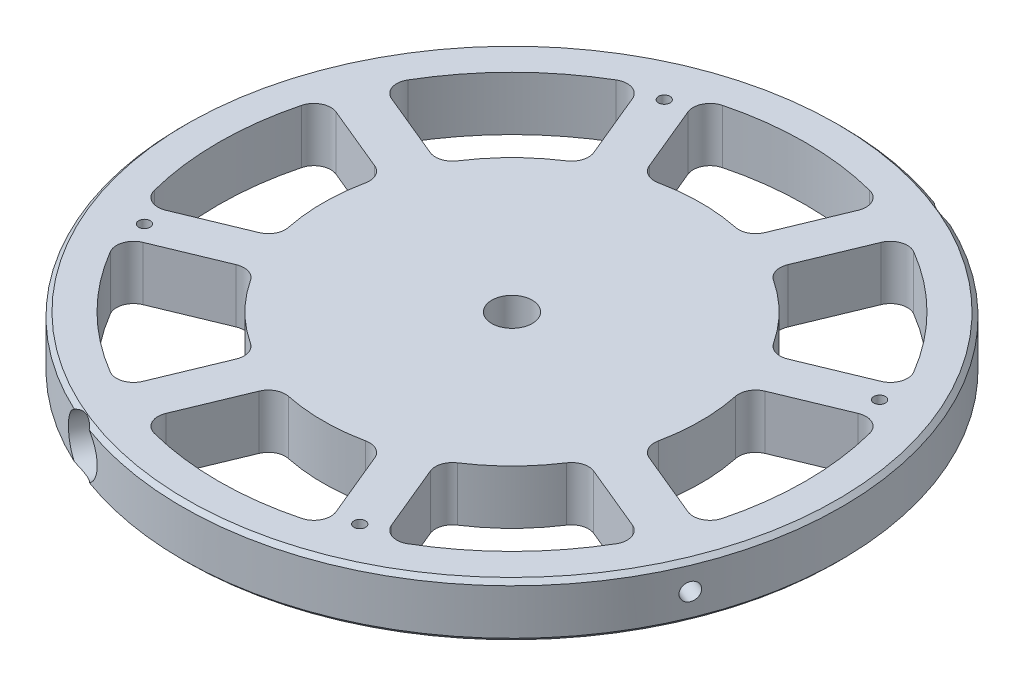
SolidWorks part; units mm, degrees
material "6061-T6 (SS)"
ref_plane "Front Plane" through (0, 0, 0) normal (0, 0, 1) x (1, 0, 0)
ref_plane "Top Plane" through (0, 0, 0) normal (0, 1, 0) x (1, 0, 0)
ref_plane "Right Plane" through (0, 0, 0) normal (1, 0, 0) x (0, 0, -1)
sketch "Sketch2" plane through (0, 0, 0) normal (1, 0, 0) x (0, 0, -1)
  line L0 (0, 0) -> (-77.55, 0)
  line L1 (-77.55, 0) -> (-77.55, 12.7)
  line L2 (-77.55, 12.7) -> (0, 12.7)
  line L5 (0, 12.7) -> (0, 0)
  dimension "D1" = 77.55
  dimension "D2" = 12.7
ref_axis "Axis1" through (0, -0.8888, 0) along (0, 1, 0)
revolve "Revolve1" add sketch "Sketch2" angle 360 about axis through (0, -0.8888, 0) along (0, 1, 0)
hole_wizard "#6-32 Tapped Hole2" positions "Sketch6" profile "Sketch7" tap size "#6-32" standard "ANSI Inch" end condition through all
sketch "Sketch6" plane through (0, 12.7, 0) normal (0, 1, 0) x (1, 0, 0)
  line L0 (0, 0) -> (-53.438, 129.0108) construction
  line L2 (0, 0) -> (0, 109.0908) construction
  point P0 (-25.3336, 61.1608)
  dimension "D1" = 22.5
  dimension "D2" = 66.2
sketch "Sketch7" plane through (-25.3336, 12.7, -61.1608) normal (1, 0, 0) x (0, 0, 1)
  line L0 (0, 0) -> (0, 12.7)
  line L1 (0, 12.7) -> (1.3525, 12.7)
  line L2 (1.3525, 12.7) -> (1.3525, 0)
  line L5 (1.3525, 0) -> (0, 0)
  line L11 (0, -6.35) -> (0, 107.95) construction
  dimension "Thread Major Dia." = 2.7051
  dimension "Thru Tap Drill Depth" = 12.7
pattern_circular "CirPattern3" count 4 over 360 about axis through (0, -0.8888, 0) along (0, 1, 0) of "#6-32 Tapped Hole2"
sketch "Sketch8" plane through (0, 12.7, 0) normal (0, 1, 0) x (1, 0, 0)
  line L4 (0, 0) -> (0, 93.9995) construction
  line L5 (0, 0) -> (113.8372, 0) construction
  line L6 (-12.2829, 42.7192) -> (-21.7355, 65.5398)
  line L7 (12.2829, 42.7192) -> (21.7355, 65.5398)
  line L8 (0, 0) -> (-25.3336, 61.1608) construction
  arc A0 (-12.2829, 42.7192) -> (12.2829, 42.7192) centre (0, 0) cw
  arc A1 (-21.7355, 65.5398) -> (21.7355, 65.5398) centre (0, 0) cw
  circle A2 centre (0, 0) radius 77.55 construction
  dimension "D1" = 44.45
  dimension "D2" = 8.5
  dimension "D3" = 5
extrude "Cut-Extrude1" cut sketch "Sketch8" against normal through all
fillet "Fillet1" radius 4 4 edges at (12.2829, 6.35, -42.7192) (21.7355, 6.35, -65.5398) (-12.2829, 6.35, -42.7192) (-21.7355, 6.35, -65.5398)
pattern_circular "CirPattern4" count 8 over 360 about axis through (0, -0.8888, 0) along (0, 1, 0) of "Cut-Extrude1", "Fillet1"
chamfer "Chamfer1" distance 1 angle 45 2 edges at (0, 0, -77.55) (0, 12.7, -77.55)
ref_plane "Plane1" through (0, 0, 0) normal (0.9239, 0, 0.3827) x (0, 1, 0)
hole_wizard "#20 (0.161) Diameter Hole1" positions "Sketch16" profile "Sketch15" hole size "#20" standard "ANSI Inch" end condition through all
sketch "Sketch16" plane through (0, 0, 0) normal (0.9239, 0, 0.3827) x (0, 1, 0)
  point P0 (6.35, 0)
  dimension "D1" = 6.35
sketch "Sketch15" plane through (0, 6.35, 0) normal (0, 1, 0) x (-0.3827, 0, 0.9239)
  line L0 (0, 0) -> (0, 101.324)
  line L1 (0, 101.324) -> (2.0447, 101.324)
  line L2 (2.0447, 101.324) -> (2.0447, 0)
  line L5 (2.0447, 0) -> (0, 0)
  line L11 (0, -6.35) -> (0, 107.95) construction
  dimension "Thru Hole Dia." = 4.0894
  dimension "Thru Hole Depth" = 101.324
ref_plane "Plane2" through (29.6771, 0, -71.6469) normal (0.3827, 0, -0.9239) x (-0.9239, 0, -0.3827)
sketch "Sketch19" plane through (29.6771, 0, -71.6469) normal (0.3827, 0, -0.9239) x (-0.9239, 0, -0.3827)
  line L0 (-76.55, 0) -> (76.55, 0) construction
  line L2 (0, -0.8888) -> (0, 13.5888) construction
  circle A0 centre (0, 6.35) radius 5.5625 construction
  circle A1 centre (0, 6.35) radius 6.25
  dimension "D1" = 12.5
  dimension "D2" = 6.35
extrude "Cut-Extrude3" cut sketch "Sketch19" against normal blind 5
pattern_circular "CirPattern5" count 2 over 360 about axis through (0, -0.8888, 0) along (0, 1, 0) of "Cut-Extrude3"
hole_wizard "#10-24 Tapped Hole1" positions "Sketch20" profile "Sketch21" tap size "#10-24" standard "ANSI Inch"
sketch "Sketch20" plane through (-27.7637, 0, 67.0275) normal (-0.3827, 0, 0.9239) x (0.9239, 0, 0.3827)
  circle A0 centre (0, 6.35) radius 6.25
  circle A1 centre (0, 6.35) radius 6.25 construction
  point P0 (0, 6.35)
sketch "Sketch21" plane through (-27.7637, 6.35, 67.0275) normal (0, 1, 0) x (0.9239, 0, 0.3827)
  line L0 (0, 0) -> (0, 51.9408)
  line L1 (0, 51.9408) -> (1.8986, 50.8)
  line L2 (1.8986, 50.8) -> (1.8986, 0)
  line L5 (1.8986, 0) -> (0, 0)
  line L10 (0, 51.9408) -> (-1.8986, 50.8) construction
  line L11 (0, -6.35) -> (0, 107.95) construction
  dimension "Tap Drill Dia." = 3.7973
  dimension "Tap Drill Depth" = 50.8
  dimension "Drill Angle" = 118
pattern_circular "CirPattern6" count 2 over 360 about axis through (0, -0.8888, 0) along (0, 1, 0) of "#10-24 Tapped Hole1"
sketch "Sketch22" plane through (0, 12.7, 0) normal (0, 1, 0) x (1, 0, 0)
  circle A0 centre (0, 0) radius 4.765
  dimension "D1" = 9.53
extrude "Cut-Extrude4" cut sketch "Sketch22" against normal blind 12.8
equation "\"TubeDiameter\" = 6.500in"
equation "\"D1@Sketch2\"=(\"TubeDiameter\"/2)-5mm"
equation "\"D2@Sketch6\"=66.2"
